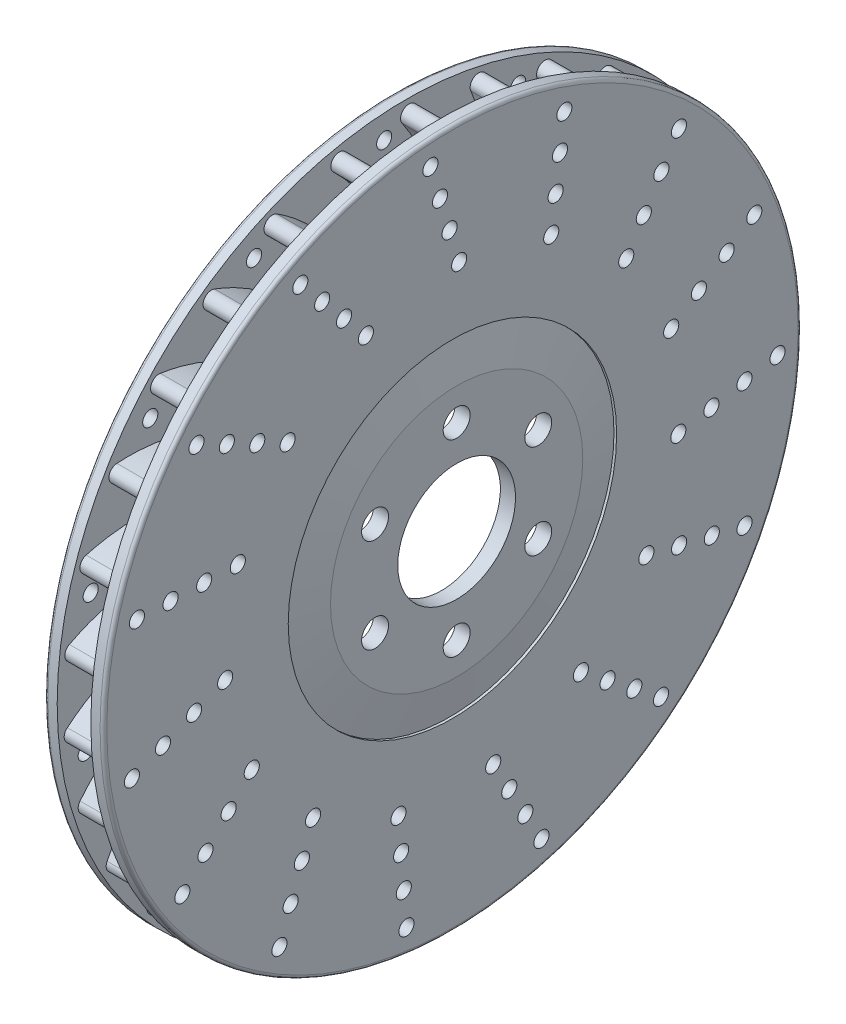
SolidWorks part; units mm, degrees
ref_plane "Front Plane" through (0, 0, 0) normal (0, 0, 1) x (1, 0, 0)
ref_plane "Top Plane" through (0, 0, 0) normal (0, 1, 0) x (1, 0, 0)
ref_plane "Right Plane" through (0, 0, 0) normal (1, 0, 0) x (0, 0, -1)
sketch "Sketch1" plane through (0, 0, 0) normal (0, 0, 1) x (1, 0, 0)
  line L0 (0, 35) -> (9, 35)
  line L1 (9, 35) -> (9, 75)
  line L2 (9, 75) -> (4.5, 100)
  line L3 (4.5, 100) -> (0, 100)
  line L4 (0, 100) -> (0, 35)
  line L5 (0, 0) -> (97.276, 0) construction
  dimension "D1" = 9
  dimension "D2" = 4.5
  dimension "D3" = 35
  dimension "D4" = 100
  dimension "D5" = 75
revolve "Revolve1" add sketch "Sketch1" angle 360 about L5
sketch "Sketch2" plane through (9, 0, 0) normal (1, 0, 0) x (0, 0, -1)
  circle A0 centre (0, 56) radius 8
  dimension "D2" = 16
  dimension "D1" = 56
extrude "Cut-Extrude1" cut sketch "Sketch2" against normal through all
pattern_circular "CirPattern1" count 6 over 360 about axis through (9, 0, 0) along (-1, 0, 0) of "Cut-Extrude1"
ref_plane "Plane1" through (-1, 0, 0) normal (-1, 0, 0) x (0, 0, 1)
sketch "Sketch3" plane through (-1, 0, 0) normal (-1, 0, 0) x (0, 0, 1)
  circle A0 centre (0, 0) radius 207.5
  circle A1 centre (0, 0) radius 125
  dimension "D1" = 415
  dimension "D2" = 82.5
extrude "Boss-Extrude1" add sketch "Sketch3" against normal blind 7.5 separate body
sketch "Sketch4" plane through (-1, 0, 0) normal (1, 0, 0) x (0, 0, -1)
  arc A0 (193.8869, 56.8548) -> (185.9829, 62.977) centre (190, 60) ccw
  circle A1 centre (0, 0) radius 125 construction
  arc A2 (124.2538, 13.6375) -> (123.4233, 19.7912) centre (0, 0) ccw
  spline S0 degree 3 poles (0, 0) (0.0074, 0) (0.0148, 0) (0.0222, 0) knots 0 0 0 0 0.000056 0.000056 0.000056 0.000056
  spline S1 degree 3 poles (0, 0) (0.0148, 0) (0.0296, 0) (0.0444, 0) knots 0 0 0 0 0.000196 0.000196 0.000196 0.000196
  spline S2 degree 3 poles (123.4233, 19.7912) (149.9271, 29.8782) (171.978, 44.0794) (185.9829, 62.977) knots 0.575555 0.575555 0.575555 0.575555 1 1 1 1
  spline S3 degree 3 poles (124.2538, 13.6375) (162.9952, 24.86) (181.366, 41.3814) (193.8869, 56.8548) knots 0.423702 0.423702 0.423702 0.423702 1 1 1 1
  circle M10 centre (0, 0) radius 125
  dimension "D1" = 10
  dimension "D2" = 60
  dimension "D3" = 190
extrude "Boss-Extrude2" add sketch "Sketch4" against normal blind 20 contours S3 S2 A0 M10 region at (-1, 37.9603, -163.3456)
ref_plane "Plane2" through (-11, 0, 0) normal (-1, 0, 0) x (0, 0, 1)
sketch "Sketch7" plane through (-21, 0, 0) normal (-1, 0, 0) x (0, 0, 1)
  circle A0 centre (0, 0) radius 207.5 construction
  circle A1 centre (0, 0) radius 207.5
  arc A2 (-124.2538, 13.6375) -> (-123.4233, 19.7912) centre (0, 0) ccw construction
  arc A3 (-124.2538, 13.6375) -> (-123.4233, 19.7912) centre (0, 0) ccw
  arc A4 (-123.4233, 19.7912) -> (-124.2538, 13.6375) centre (0, 0) ccw construction
  arc A5 (-123.4233, 19.7912) -> (-124.2538, 13.6375) centre (0, 0) ccw
extrude "Boss-Extrude3" add sketch "Sketch7" along normal blind 7.5
sketch "Sketch6" plane through (-11, 0, 0) normal (-1, 0, 0) x (0, 0, 1)
  line L0 (-4, 135.4614) -> (-4, 207.4614) construction
  line L1 (-4, 135.4614) -> (21.4028, 220.9968) construction
  circle A0 centre (-4, 135.4614) radius 4.5
  point P2 (0, 0)
  point P5 (0, 0)
  point P6 (48.5361, 197.5277)
  point P8 (0, 0)
  point P9 (0, 0)
  point P10 (24.249, 195.6001)
  point P11 (21.4028, 220.9968)
  dimension "D1" = 9
  dimension "D2" = 4
  dimension "D3" = 72
extrude "Cut-Extrude2" cut sketch "Sketch6" against normal blind 37.5 and the other way blind 52
pattern_linear "LPattern1" count 4 spacing 20 along (0, 0.9586, 0.2847) of "Cut-Extrude2"
pattern_circular "CirPattern5" count 15 over 360 about axis through (6.5, 0, 0) along (-1, 0, 0) of "LPattern1"
pattern_circular "CirPattern14" count 30 over 360 about axis through (-28.5, 0, 0) along (-1, 0, 0) of "Boss-Extrude2"
sketch "Sketch8" plane through (6.5, 0, 0) normal (1, 0, 0) x (0, 0, -1)
  circle A0 centre (0, 0) radius 128.1045
  circle A1 centre (0, 0) radius 97.6361
extrude "Boss-Extrude4" add sketch "Sketch8" against normal offset from surface (6.5 mm away) 1 up to face at (-1, 0, 0)
fillet "Fillet2" radius 2 2 edges at (-28.5, 0, 207.5) (6.5, 0, 207.5)
